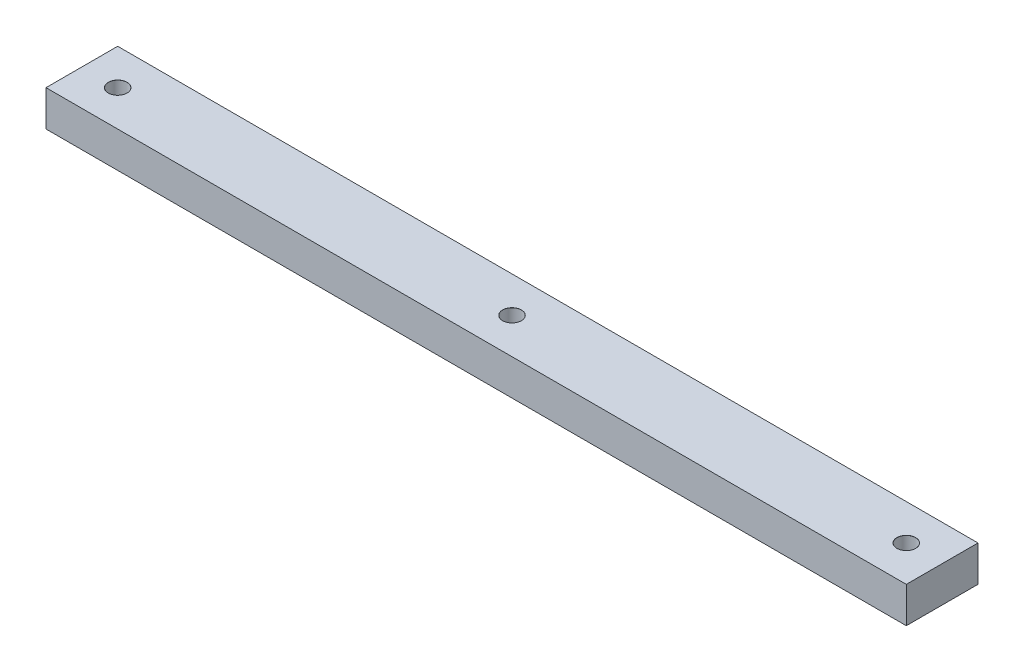
SolidWorks part; units mm, degrees
ref_plane "Front Plane" through (0, 0, 0) normal (0, 0, 1) x (1, 0, 0)
ref_plane "Top Plane" through (0, 0, 0) normal (0, 1, 0) x (1, 0, 0)
ref_plane "Right Plane" through (0, 0, 0) normal (1, 0, 0) x (0, 0, -1)
sketch "Sketch1" plane through (0, 0, 0) normal (0, 1, 0) x (1, 0, 0)
  line L0 (0, 0) -> (0, 37.5156) construction
  line L1 (152.4, -12.7) -> (-152.4, -12.7)
  line L2 (152.4, -12.7) -> (152.4, 12.7)
  line L3 (152.4, 12.7) -> (-152.4, 12.7)
  line L4 (-152.4, -12.7) -> (-152.4, 12.7)
  line L5 (152.4, -12.7) -> (-152.4, 12.7) construction
  line L6 (152.4, 12.7) -> (-152.4, -12.7) construction
  point P0 (0, 0)
  point P6 (-139.7, 0)
  point P8 (-152.4, 0)
  point P10 (139.7, 0)
  dimension "D1" = 304.8
  dimension "D2" = 25.4
  dimension "D3" = 12.7
extrude "Boss-Extrude1" add sketch "Sketch1" along normal blind 12.7
hole_wizard "M6 Clearance Hole1" positions "3DSketch1" profile "Sketch2" hole size "M6" standard "ANSI Metric" end condition through all
sketch3d "3DSketch1"
  point P0 (0, 12.7, 0)
  point P4 (-139.7, 12.7, 0)
  point P6 (139.7, 12.7, 0)
  point P11 (0, 0, 0)
  point P12 (0, 0, 0)
sketch "Sketch2" plane through (0, 12.7, 0) normal (1, 0, 0) x (0, 0, 1)
  line L0 (0, 0) -> (0, 12.7)
  line L1 (0, 12.7) -> (3.3, 12.7)
  line L2 (3.3, 12.7) -> (3.3, 0.025)
  line L3 (3.3, 0.025) -> (3.325, 0)
  line L5 (3.325, 0) -> (0, 0)
  line L6 (-3.3, 0.025) -> (-3.325, 0) construction
  line L11 (0, -6.35) -> (0, 107.95) construction
  dimension "Thru Hole Dia." = 6.6
  dimension "Thru Hole Depth" = 12.7
  dimension "Near C'Sink Dia." = 6.65
  dimension "Near C'Sink Angle" = 90
equation "\"Rover_Length\"= 25in"
equation "\"Rover_Width\"= 18in"
equation "\"Rover_Height\"= 12in"
equation "\"Chassis_Wheelbase\"= 28in"
equation "\"Chassis_WheelDiam\"= 171mm"
equation "\"Chassis_ArmDiamWidth\"= 0.75in"
equation "\"Chassis_ArmAngle\"= 135deg"
equation "\"Chassis_ArmHeight\"= 8in"
equation "\"Chassis_HubMountOD\"= 3in"
equation "\"Chassis_WheelBoltHole\"= 36mm"
equation "\"Chassis_WheelBoltNum\"= 4"
equation "\"Chassis_DiffBarLength\"= 12in"
equation "\"Chassis_DiffBarWidth\"= 1in"
equation "\"Chassis_DiffBarHeight\"= 0.5in"
equation "\"Chassis_DiffLinkage_Length\"= 2.5in"
equation "\"Chassis_MountBracketThickness\"= 0.125in"
equation "\"Chassis_MountBracketWidth\"= 3in"
equation "\"Chassis_MountBacketOverlap\"= 0.5in"
equation "\"Chassis_ArmShaftDiam\"= 0.75in"
equation "\"Chassis_ArmHoleSpacing\" = 1.25in"
equation "\"D1@Sketch1\"=\"Chassis_DiffBarLength\""
equation "\"D2@Sketch1\"=\"Chassis_DiffBarWidth\""
equation "\"D1@Boss-Extrude1\"=\"Chassis_DiffBarHeight\""
